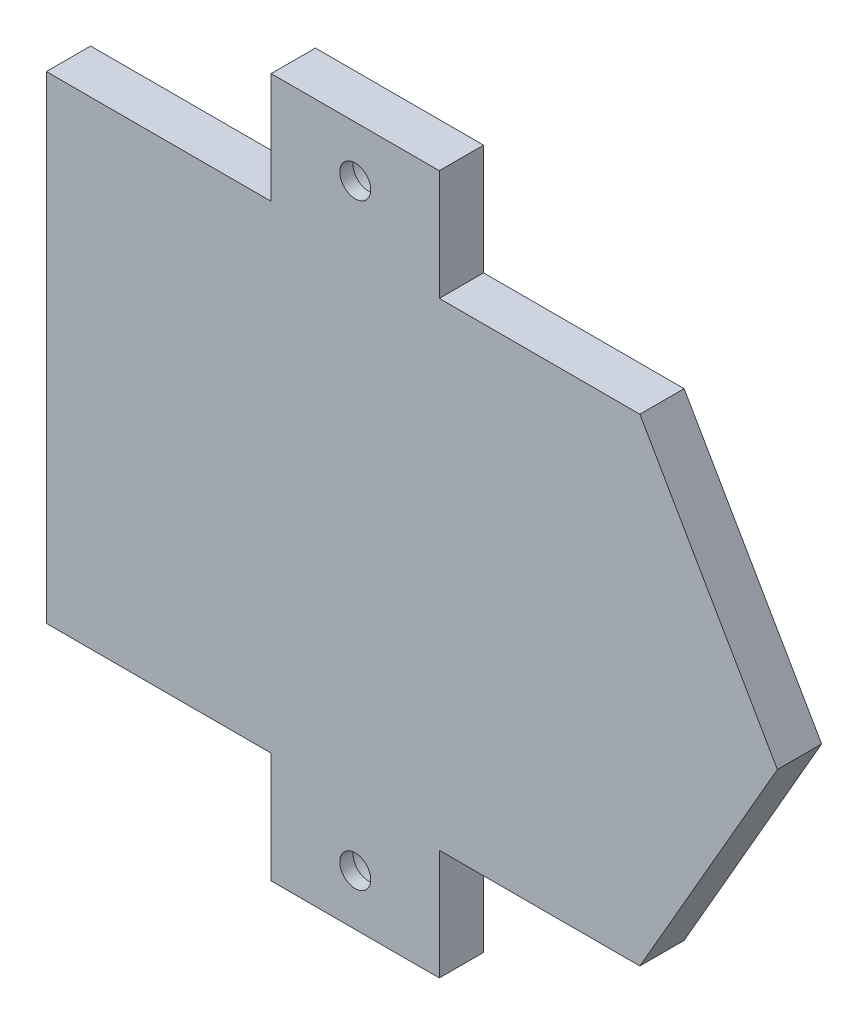
SolidWorks part; units mm, degrees
ref_plane "Front Plane" through (0, 0, 0) normal (0, 0, 1) x (1, 0, 0)
ref_plane "Top Plane" through (0, 0, 0) normal (0, 1, 0) x (1, 0, 0)
ref_plane "Right Plane" through (0, 0, 0) normal (1, 0, 0) x (0, 0, -1)
sketch "Sketch1" plane through (0, 0, 0) normal (0, 0, 1) x (1, 0, 0)
  line L0 (73.8, 50) -> (85.6, 50) construction
  line L1 (17, 70.5) -> (73.8, 70.5) construction
  line L2 (17, 70.5) -> (17, 29.5) construction
  line L3 (17, 29.5) -> (73.8, 29.5) construction
  line L4 (73.8, 70.5) -> (73.8, 29.5) construction
  line L5 (73.8, 70.5) -> (85.6, 50) construction
  line L6 (85.6, 50) -> (73.8, 29.5) construction
  line L7 (17, 29.5) -> (73.8, 70.5) construction
  line L8 (17, 70.5) -> (73.8, 29.5) construction
  line L10 (10, 77.5) -> (10, 22.5)
  line L11 (45.4, 50) -> (0, 50) construction
  line L13 (14, 73.5) -> (75.5347, 73.5)
  line L14 (75.5347, 73.5) -> (89.0615, 50)
  line L15 (89.0615, 50) -> (75.5347, 26.5)
  line L16 (14, 26.5) -> (75.5347, 26.5)
  line L17 (14, 73.5) -> (14, 26.5)
  line L18 (10, 77.5) -> (77.8476, 77.5)
  line L19 (77.8476, 77.5) -> (93.6768, 50)
  line L20 (93.6768, 50) -> (77.8476, 22.5)
  line L21 (10, 22.5) -> (77.8476, 22.5)
  line L24 (35.4, 77.5) -> (55.4, 77.5)
  line L25 (35.4, 77.5) -> (35.4, 90)
  line L26 (35.4, 90) -> (55.4, 90)
  line L27 (55.4, 77.5) -> (55.4, 90)
  line L33 (35.4, 22.5) -> (55.4, 22.5)
  line L34 (35.4, 22.5) -> (35.4, 10)
  line L35 (35.4, 10) -> (55.4, 10)
  line L36 (55.4, 22.5) -> (55.4, 10)
  line L38 (45.4, 90) -> (45.4, 10) construction
  line L40 (77.8476, 77.5) -> (90, 77.5)
  line L41 (77.8476, 77.5) -> (77.8476, 22.5)
  line L42 (77.8476, 22.5) -> (90, 22.5)
  line L43 (90, 77.5) -> (90, 22.5)
  line L44 (10, 77.5) -> (10, 22.5) construction
  point P6 (45.4, 50)
  dimension "D1" = 41
  dimension "D2" = 56.8
  dimension "D3" = 11.8
  dimension "D6" = 20
  dimension "D4" = 3
  dimension "D5" = 4
extrude "Boss-Extrude2" add sketch "Sketch1" along normal blind 5 contours L41 L18 L10 L21 L15 L16 L17 L13 L14 | L18 L27 L26 L25 | L43 L19 L41 L14 L15 L20 | L14 L41 L15 | L41 L14 L13 L17 L16 L15 | L36 L21 L34 L35 | L19 L43 L20 region at (22.7, 76.6266, 0) region at (45.4, 83.75, 0) region at (45.4, 16.25, 0) region at (83.4356, 66.6629, 0) region at (91.2256, 50, 0) region at (45.827, 50, 0) region at (81.5855, 50, 0)
sketch "Sketch6" plane through (0, 0, 0) normal (0, 0, 1) x (1, 0, 0)
  line L13 (55.4, 22.5) -> (77.8476, 22.5)
  line L14 (77.8476, 22.5) -> (93.6768, 50)
  line L15 (93.6768, 50) -> (77.8476, 77.5)
  line L16 (77.8476, 77.5) -> (55.4, 77.5)
  line L17 (55.4, 77.5) -> (55.4, 90)
  line L18 (55.4, 90) -> (35.4, 90)
  line L19 (35.4, 90) -> (35.4, 77.5)
  line L20 (35.4, 77.5) -> (10, 77.5)
  line L21 (10, 77.5) -> (10, 22.5)
  line L22 (10, 22.5) -> (35.4, 22.5)
  line L23 (35.4, 22.5) -> (35.4, 10)
  line L24 (35.4, 10) -> (55.4, 10)
  line L25 (55.4, 10) -> (55.4, 22.5)
  line L26 (55.4, 22.5) -> (77.8476, 22.5)
  line L27 (77.8476, 22.5) -> (93.6768, 50)
  line L28 (93.6768, 50) -> (77.8476, 77.5)
  line L29 (77.8476, 77.5) -> (55.4, 77.5)
  line L30 (55.4, 77.5) -> (55.4, 90)
  line L31 (55.4, 90) -> (35.4, 90)
  line L32 (35.4, 90) -> (35.4, 77.5)
  line L33 (35.4, 77.5) -> (10, 77.5)
  line L34 (10, 77.5) -> (10, 22.5)
  line L35 (10, 22.5) -> (35.4, 22.5)
  line L36 (35.4, 22.5) -> (35.4, 10)
  line L37 (35.4, 10) -> (55.4, 10)
  line L38 (55.4, 10) -> (55.4, 22.5)
  line L52 (54.9, 23) -> (77.5584, 23)
  line L53 (77.5584, 23) -> (93.0999, 50)
  line L54 (93.0999, 50) -> (77.5584, 77)
  line L55 (77.5584, 77) -> (54.9, 77)
  line L56 (54.9, 77) -> (54.9, 89.5)
  line L57 (54.9, 89.5) -> (35.9, 89.5)
  line L58 (35.9, 89.5) -> (35.9, 77)
  line L59 (35.9, 77) -> (10.5, 77)
  line L60 (10.5, 77) -> (10.5, 23)
  line L61 (10.5, 23) -> (35.9, 23)
  line L62 (35.9, 23) -> (35.9, 10.5)
  line L63 (35.9, 10.5) -> (54.9, 10.5)
  line L64 (54.9, 10.5) -> (54.9, 23)
  line L65 (54.9, 23) -> (77.5584, 23)
  line L66 (77.5584, 23) -> (93.0999, 50)
  line L67 (93.0999, 50) -> (77.5584, 77)
  line L68 (77.5584, 77) -> (54.9, 77)
  line L69 (54.9, 77) -> (54.9, 89.5)
  line L70 (54.9, 89.5) -> (35.9, 89.5)
  line L71 (35.9, 89.5) -> (35.9, 77)
  line L72 (35.9, 77) -> (10.5, 77)
  line L73 (10.5, 77) -> (10.5, 23)
  line L74 (10.5, 23) -> (35.9, 23)
  line L75 (35.9, 23) -> (35.9, 10.5)
  line L76 (35.9, 10.5) -> (54.9, 10.5)
  line L77 (54.9, 10.5) -> (54.9, 23)
  dimension "D1" = 0
  dimension "D2" = 0.5
extrude "Cut-Extrude6" cut sketch "Sketch6" along normal through all contours L37 L38 L26 L27 L28 L29 L30 L31 L32 L33 L34 L35 L36 L77 L76 L75 L74 L73 L72 L71 L70 L69 L68 L67 L66 L65 region at (55.2842, 16.25, 0)
sketch "Sketch2" plane through (0, 0, 0) normal (0, 0, 1) x (1, 0, 0)
  line L0 (35.4, 77.5) -> (55.4, 90) construction
  line L1 (35.4, 22.5) -> (55.4, 10) construction
  circle A0 centre (45.4, 16.25) radius 1.75
  circle A1 centre (45.4, 83.75) radius 3.5
  circle A2 centre (45.4, 83.75) radius 1.75
  circle A3 centre (45.4, 16.25) radius 3.5
  point P14 (35.4, 77.5)
  point P15 (35.9, 77)
  point P17 (54.9, 89.5)
  point P19 (35.9, 23)
  point P21 (54.9, 10.5)
  point P23 (35.4, 77.5)
  point P25 (55.4, 90)
  point P27 (55.4, 10)
  point P29 (35.4, 22.5)
  dimension "D1" = 7
  dimension "D2" = 3.5
extrude "Cut-Extrude2" cut sketch "Sketch2" against normal through all and the other way through all contours A2 | A0 region at (45.4, 16.25, 0) region at (45.4, 83.75, 0)
extrude "Cut-Extrude4" cut sketch "Sketch2<3>" along normal blind 3.5 contours A1 A2 | A3 A0 region at (41.999, 83.75, 0) region at (41.999, 16.25, 0)
sketch "Sketch2<3>" plane through (0, 0, 0) normal (0, 0, 1) x (1, 0, 0) same geometry as "Sketch2"
